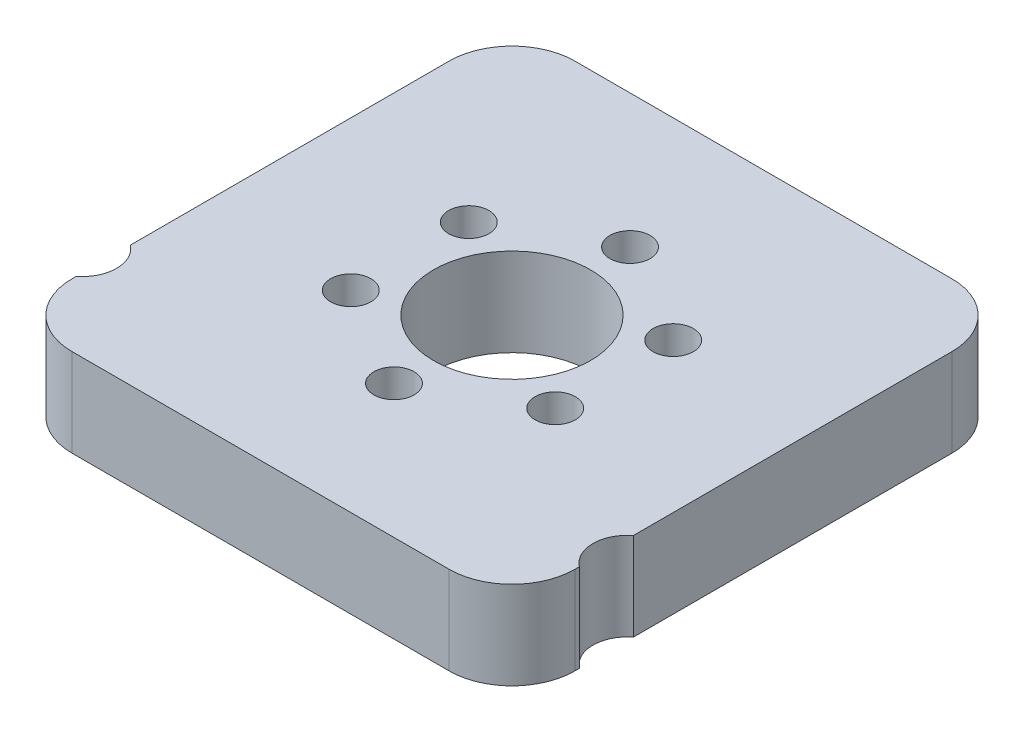
SolidWorks part; units mm, degrees
ref_plane "Front Plane" through (0, 0, 0) normal (0, 0, 1) x (1, 0, 0)
ref_plane "Top Plane" through (0, 0, 0) normal (0, 1, 0) x (1, 0, 0)
ref_plane "Right Plane" through (0, 0, 0) normal (1, 0, 0) x (0, 0, -1)
sketch "Sketch1" plane through (0, 0, 0) normal (0, 1, 0) x (1, 0, 0)
  line L0 (0, 0) -> (0, 35.4208) construction
  line L1 (-20, -20) -> (20, -20)
  line L2 (-20, -20) -> (-20, 20)
  line L3 (-20, 20) -> (20, 20)
  line L4 (20, -20) -> (20, 20)
  line L5 (-20, -20) -> (20, 20) construction
  line L6 (-20, 20) -> (20, -20) construction
  circle A0 centre (0, 0) radius 6.25
  circle A1 centre (0, 25) radius 2.7073
  circle A2 centre (21.6506, -12.5) radius 2.7073
  circle A3 centre (-21.6506, -12.5) radius 2.7073
  point P0 (0, 0)
  point P18 (0, 0)
  dimension "D2" = 12.5
  dimension "D1" = 25
  dimension "D3" = 40
  dimension "D4" = 40
  dimension "D5" = 3
extrude "Boss-Extrude1" add sketch "Sketch1" along normal blind 7 contours A3 L2 L1 L4 A2 L3 A0 region at (-19.4343, 0, 17.3229)
sketch "Sketch7" plane through (0, 7, 0) normal (0, 1, 0) x (1, 0, 0)
  circle A0 centre (0, 0) radius 22.5
  circle A1 centre (0, 0) radius 6.25
  dimension "D1" = 45
  dimension "D2" = 12.5
extrude "Boss-Extrude2" [suppressed] add sketch "Sketch7" along normal blind 5
sketch "Sketch5" [suppressed] plane through (0, 0, 0) normal (1, 0, 0) x (0, 0, -1)
  line L0 (-10.331, 15) -> (10.331, 0) construction
  line L1 (10, 5) -> (-10, 5)
  line L2 (10, 5) -> (10, 10)
  line L3 (10, 10) -> (-10, 10)
  line L4 (-10, 5) -> (-10, 10)
  line L5 (10, 5) -> (-10, 10) construction
  line L6 (10, 10) -> (-10, 5) construction
  line L7 (20, 7.5) -> (-20, 7.5) construction
  line L8 (20, 15) -> (20, 0) construction
  line L9 (-20, 15) -> (-20, 0) construction
  line L10 (-10.3541, 15) -> (-10.3078, 15) construction
  line L11 (-10.3541, 0) -> (20, 0) construction
  point P0 (0, 7.5)
  dimension "D1" = 20
  dimension "D2" = 5
extrude "Square side-insert" [suppressed] cut sketch "Sketch5" against normal up to surface (20 mm away) up to face at (-20, 3.5, -4.8229)
sketch "Sketch3" [suppressed] plane through (0, 0, -20) normal (0, 0, -1) x (-1, 0, 0)
  line L3 (15.1539, 15) -> (15.1539, 3) construction
  line L4 (20, 15) -> (10.3078, 15) construction
  circle A0 centre (15.1539, 3) radius 1.6
  dimension "D2" = 3.2
  dimension "D1" = 12
extrude "Single Screw" [suppressed] cut sketch "Sketch3" against normal blind 17
sketch "Sketch2" [suppressed] plane through (0, 0, 20) normal (0, 0, 1) x (1, 0, 0)
  line L0 (0, 27.8717) -> (0, -11.9207) construction
  line L1 (20, 2) -> (10, 2)
  line L3 (10, 2) -> (10, 0)
  line L4 (-20, 0) -> (20, 0) construction
  line L5 (20, 15) -> (20, 0) construction
  circle A0 centre (10, 2) radius 1.6
  circle A1 centre (-10, 2) radius 1.6
  dimension "D3" = 3.2
  dimension "D1" = 10
  dimension "D2" = 2
extrude "Double Screw" [suppressed] cut sketch "Sketch2" against normal blind 10 contours A1 | A0
sketch "Sketch6" plane through (0, 7, 0) normal (0, 1, 0) x (1, 0, 0)
  circle A9 centre (0, -9.385) radius 1.6
  circle A10 centre (-8.1276, -4.6925) radius 1.6
  circle A11 centre (-8.1276, 4.6925) radius 1.6
  circle A12 centre (0, 9.385) radius 1.6
  circle A13 centre (8.1276, 4.6925) radius 1.6
  circle A14 centre (8.1276, -4.6925) radius 1.6
  point P16 (0, 0)
  dimension "D2" = 9.385
  dimension "D1" = 3.2
  dimension "D3" = 9.385
extrude "Cut-Extrude1" cut sketch "Sketch6" against normal through all
sketch "Sketch8" [suppressed] plane through (0, 12, 0) normal (0, 1, 0) x (1, 0, 0)
  line L0 (-20, 5) -> (-20, -5)
  line L1 (-20, -5) -> (-3.75, -5) construction
  line L2 (-20, 5) -> (-3.75, 5) construction
  line L3 (-20, -10.3541) -> (-20, -10.3078) construction
  line L4 (-20, 5) -> (-20, 12.5)
  line L6 (-20, -5) -> (-20, -12.5)
  line L8 (-20, 12.5) -> (-13.9645, 6.4645)
  line L9 (-10.4289, 5) -> (-3.75, 5)
  line L10 (-20, -12.5) -> (-13.9645, -6.4645)
  line L11 (-10.4289, -5) -> (-3.75, -5)
  circle A0 centre (0, 0) radius 6.25 construction
  arc A1 (-3.75, 5) -> (-3.75, -5) centre (0, 0) ccw
  arc A2 (-13.9645, -6.4645) -> (-10.4289, -5) centre (-10.4289, -10) cw
  arc A3 (-10.4289, 5) -> (-13.9645, 6.4645) centre (-10.4289, 10) cw
  point P6 (-20, 0)
  point P19 (-12.5, -5)
  point P22 (-12.5, 5)
  dimension "D2" = 7.5
  dimension "D5" = 5
  dimension "D1" = 10
  dimension "D3" = 7.5
  dimension "D4" = 7.5
extrude "Cut-Extrude3" [suppressed] cut sketch "Sketch8" against normal blind 5 from offset 5 offset against normal yes
fillet "Fillet2" radius 5 4 edges at (20, 3.5, 20) (20, 3.5, -20) (-20, 3.5, -20) (-20, 3.5, 20)
fillet "Fillet3" [suppressed] radius 3
